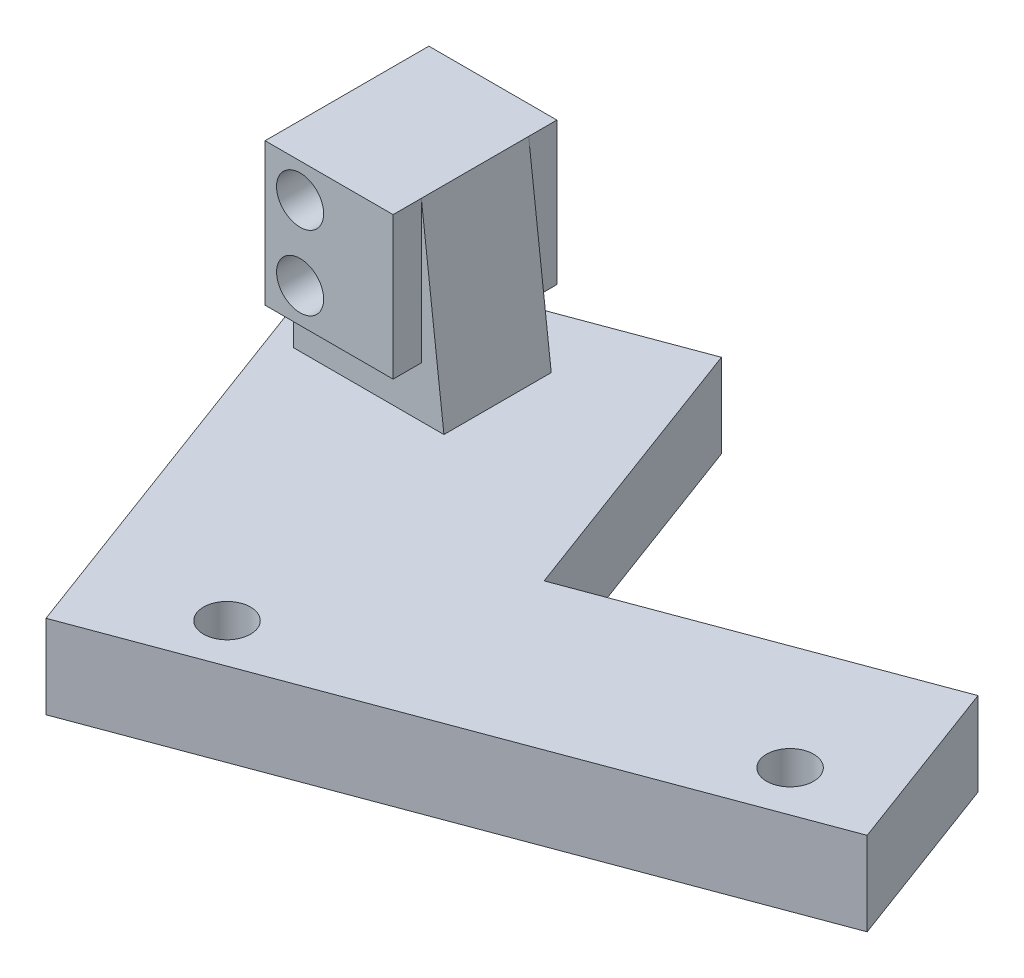
SolidWorks part; units mm, degrees
ref_plane "Front Plane" through (0, 0, 0) normal (0, 0, 1) x (1, 0, 0)
ref_plane "Top Plane" through (0, 0, 0) normal (0, 1, 0) x (1, 0, 0)
ref_plane "Right Plane" through (0, 0, 0) normal (1, 0, 0) x (0, 0, -1)
sketch "Sketch1" plane through (0, 0, 0) normal (0, 0, 1) x (1, 0, 0)
  line L0 (-111.8199, 128.5717) -> (-91.4999, 128.5717)
  line L1 (-122.8766, 128.5659) -> (-97.86, 128.5791) construction
  line L2 (-91.4999, 128.5717) -> (-91.4999, 102.49)
  line L3 (-91.4999, 102.49) -> (-111.8199, 102.49)
  line L4 (-111.8199, 102.49) -> (-111.8199, 128.5717)
  circle A0 centre (-104.0505, 124) radius 3.175
  circle A1 centre (-104.0452, 114) radius 3.175
  dimension "D4" = 6.35
  dimension "D5" = 6.35
  dimension "D1" = 20.32
  dimension "D2" = 6.35
  dimension "D3" = 3.81
extrude "Boss-Extrude1" add sketch "Sketch1" along normal up to surface (22.098 mm away)
ref_plane "Plane1" through (0, 102.49, 0) normal (0, 1, 0) x (1, 0, 0)
sketch "Sketch2" plane through (0, 102.49, 0) normal (0, 1, 0) x (1, 0, 0)
  line L4 (-91.4999, -22.098) -> (-111.8199, -22.098) construction
  line L6 (-93.8327, -66.5977) -> (-13.0724, -36.5641)
  line L9 (-116.8518, -4.6994) -> (-93.8327, -66.5977)
  line L10 (-116.8518, -4.6994) -> (-78.7605, 9.4662)
  line L11 (-78.7605, 9.4662) -> (-64.5949, -28.6251)
  line L12 (-64.5949, -28.6251) -> (-21.9259, -12.757)
  line L13 (-21.9259, -12.757) -> (-13.0724, -36.5641)
  circle A0 centre (-81.3473, -54.66) radius 3.175
  circle A1 centre (-26.1725, -33.8627) radius 3.175
  circle A2 centre (-81.3473, -54.66) radius 3.175 construction
  circle A3 centre (-26.1725, -33.8627) radius 3.175 construction
  dimension "D5" = 15.24
  dimension "D9" = 6.35
  dimension "D10" = 6.35
  dimension "D2" = 25.4
  dimension "D3" = 66.04
  dimension "D4" = 40.64
  dimension "D6" = 40.8958
  dimension "D7" = 86.164
  dimension "D8" = 69.601
extrude "Boss-Extrude2" add sketch "Sketch2" against normal up to surface (11.2786 mm away)
sketch "Sketch3" plane through (-91.4999, 0, 0) normal (1, 0, 0) x (0, 0, -1)
  line L1 (-22.098, 102.49) -> (-18.288, 102.49)
  line L2 (-22.098, 102.49) -> (-22.098, 109.348)
  line L3 (-22.098, 109.348) -> (-18.288, 109.348)
  line L4 (-18.288, 102.49) -> (-18.288, 109.348)
  line L5 (0, 102.49) -> (-3.81, 102.49)
  line L6 (0, 102.49) -> (0, 109.348)
  line L7 (0, 109.348) -> (-3.81, 109.348)
  line L8 (-3.81, 102.49) -> (-3.81, 109.348)
  dimension "D1" = 3.81
  dimension "D2" = 6.858
  dimension "D3" = 3.81
  dimension "D4" = 6.858
extrude "Cut-Extrude1" cut sketch "Sketch3" against normal blind 30.48
sketch "Sketch4" plane through (0, 0, 22.098) normal (0, 0, 1) x (1, 0, 0)
  line L0 (277.0348, 102.49) -> (-277.0348, 102.49) construction
  line L1 (-111.8199, 128.5717) -> (-108.7719, 128.5717)
  line L2 (-111.8199, 128.5717) -> (-111.8199, 102.49)
  line L3 (-111.8199, 102.49) -> (-108.7719, 102.49)
  line L4 (-108.7719, 128.5717) -> (-108.7719, 102.49)
  dimension "D1" = 3.048
extrude "Cut-Extrude2" cut sketch "Sketch4" against normal blind 27.686
ref_plane "Plane2" through (0, 0, 11.049) normal (0, 0, -1) x (-1, 0, 0)
ref_plane "Plane3" through (0, 0, 11.049) normal (0, 0, -1) x (-1, 0, 0)
sketch "Sketch6" plane through (0, 0, 11.049) normal (0, 0, -1) x (-1, 0, 0)
  line L0 (91.4999, 128.5717) -> (91.4999, 102.49)
  line L1 (277.0348, 102.49) -> (-277.0348, 102.49) construction
  line L2 (91.4999, 102.49) -> (88.4519, 102.49)
  line L3 (88.4519, 102.49) -> (91.4999, 128.5717)
  dimension "D1" = 3.048
extrude "Boss-Extrude3" add sketch "Sketch6" along direction (0, 0, 1) on the side of the normal up to surface (7.239 mm away) and the other way up to surface (7.239 mm away) up to face at (-100.1359, 105.919, 3.81) other way up to face at (-100.1359, 105.919, 18.288)
